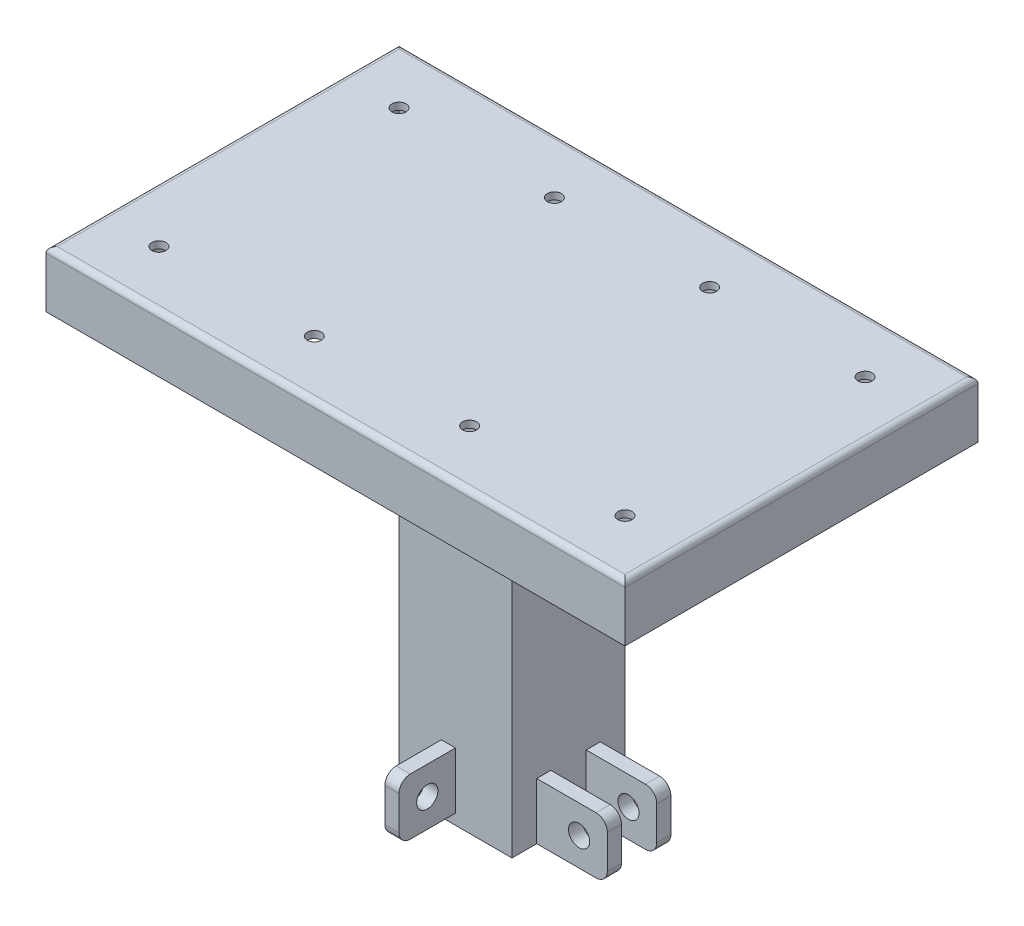
SolidWorks part; units mm, degrees
material "Alloy Steel"
ref_plane "Front Plane" through (0, 0, 0) normal (0, 0, 1) x (1, 0, 0)
ref_plane "Top Plane" through (0, 0, 0) normal (0, 1, 0) x (1, 0, 0)
ref_plane "Right Plane" through (0, 0, 0) normal (1, 0, 0) x (0, 0, -1)
other "Configuration Table"
sketch "Sketch1" plane through (0, 0, 0) normal (0, 1, 0) x (1, 0, 0)
  line L1 (-130.175, 79.375) -> (130.175, 79.375)
  line L2 (-130.175, 79.375) -> (-130.175, -79.375)
  line L3 (-130.175, -79.375) -> (130.175, -79.375)
  line L4 (130.175, 79.375) -> (130.175, -79.375)
  line L5 (-130.175, 79.375) -> (130.175, -79.375) construction
  line L6 (-130.175, -79.375) -> (130.175, 79.375) construction
  point P0 (0, 0)
  dimension "D1" = 260.35
  dimension "D2" = 158.75
extrude "Boss-Extrude1" add sketch "Sketch1" along normal blind 25.4
shell "Shell1" thickness 3.175 removed face at (0, 0, 0)
sketch "Sketch2" plane through (0, 22.225, 0) normal (0, -1, 0) x (1, 0, 0)
  line L1 (-25.4, 25.4) -> (25.4, 25.4)
  line L2 (-25.4, 25.4) -> (-25.4, -25.4)
  line L3 (-25.4, -25.4) -> (25.4, -25.4)
  line L4 (25.4, 25.4) -> (25.4, -25.4)
  line L5 (-25.4, 25.4) -> (25.4, -25.4) construction
  line L6 (-25.4, -25.4) -> (25.4, 25.4) construction
  point P0 (0, 0)
  dimension "D1" = 50.8
extrude "Boss-Extrude2" add sketch "Sketch2" along normal blind 184.15
shell "Shell2" thickness 3.175 removed face at (0, -161.925, 0)
sketch "Sketch4" plane through (0, 0, 0) normal (0, 0, 1) x (1, 0, 0)
  line L0 (25.4, -9.525) -> (63.5, 22.225)
  line L1 (25.4, -161.925) -> (25.4, 22.225) construction
  line L2 (123.0141, 22.225) -> (63.5, 22.225)
  line L4 (-130.175, 25.4) -> (130.175, 25.4) construction
  line L5 (25.4, -59.1201) -> (123.0141, 22.225)
  line L8 (63.5, 22.225) -> (25.4, 22.225) construction
  line L9 (-12.7, -90.8701) -> (168.7341, 60.325) construction
  line L10 (168.7341, 60.325) -> (-12.7, 60.325) construction
  line L11 (-12.7, 60.325) -> (-12.7, -90.8701) construction
  line L12 (25.4, -9.525) -> (25.4, -59.1201)
  line L14 (25.4, 22.225) -> (25.4, -9.525) construction
  dimension "D3" = 3.175
  dimension "D4" = 38.1
extrude "Boss-Extrude3" add sketch "Sketch4" along normal mid plane 6.35
mirror "Mirror1" about plane through (0, 0, 0) normal (1, 0, 0) of "Boss-Extrude3"
fillet "Fillet1" radius 2.54 4 edges at (-130.175, 25.4, 0) (0, 25.4, -79.375) (130.175, 25.4, 0) (0, 25.4, 79.375)
ref_plane "Plane1" through (0, 0, 14.2875) normal (0, 0, 1) x (1, 0, 0)
sketch "Sketch6" plane through (0, 0, 14.2875) normal (0, 0, 1) x (1, 0, 0)
  line L0 (25.4, -161.925) -> (57.15, -161.925)
  line L1 (57.15, -161.925) -> (57.15, -136.525)
  line L2 (57.15, -136.525) -> (25.4, -136.525)
  line L3 (25.4, -161.925) -> (25.4, 22.225) construction
  line L4 (25.4, -136.525) -> (25.4, -161.925)
  circle A0 centre (44.45, -149.225) radius 4.7625
  dimension "D3" = 9.525
  dimension "D1" = 31.75
  dimension "D2" = 25.4
  dimension "D4" = 12.7
  dimension "D5" = 12.7
extrude "Boss-Extrude4" add sketch "Sketch6" against normal blind 6.35
mirror "Mirror2" about plane through (0, 0, 0) normal (0, 0, 1) of "Boss-Extrude4"
fillet "Fillet2" radius 5.08 4 edges at (57.15, -161.925, -11.1125) (57.15, -136.525, -11.1125) (57.15, -161.925, 11.1125) (57.15, -136.525, 11.1125)
ref_plane "Plane2" through (0, 0, 0) normal (1, 0, 0) x (0, 0, -1)
sketch "Sketch7" plane through (0, 0, 0) normal (1, 0, 0) x (0, 0, -1)
  line L0 (-25.4, -157.1625) -> (-50.8, -157.1625)
  line L1 (-25.4, -161.925) -> (-25.4, 22.225) construction
  line L2 (-50.8, -157.1625) -> (-50.8, -131.7625)
  line L3 (-50.8, -131.7625) -> (-25.4, -131.7625)
  line L4 (-25.4, -131.7625) -> (-25.4, -157.1625)
  line L5 (-14.2875, -161.925) -> (-25.4, -161.925) construction
  circle A0 centre (-38.1, -144.4625) radius 4.7625
  dimension "D3" = 9.525
  dimension "D1" = 25.4
  dimension "D2" = 4.7625
  dimension "D4" = 12.7
  dimension "D5" = 12.7
extrude "Boss-Extrude5" add sketch "Sketch7" against normal blind 6.35
fillet "Fillet3" radius 5.08 2 edges at (-3.175, -157.1625, 50.8) (-3.175, -131.7625, 50.8)
mirror "Mirror3" about plane through (0, 0, 0) normal (0, 0, 1) of "Fillet3", "Boss-Extrude5"
hole_wizard "1/4 (0.25) Diameter Hole1" positions "Sketch8" profile "Sketch9" hole size "1/4" standard "ANSI Inch" end condition through all
sketch "Sketch8" plane through (0, 25.4, 0) normal (0, 1, 0) x (1, 0, 0)
  line L0 (-130.175, -79.375) -> (-130.175, 79.375) construction
  line L1 (-130.175, 79.375) -> (130.175, 79.375) construction
  line L2 (130.175, 79.375) -> (130.175, -79.375) construction
  point P0 (-104.775, 53.975)
  point P2 (-34.925, 53.975)
  point P4 (34.925, 53.975)
  point P6 (104.775, 53.975)
  dimension "D1" = 25.4
  dimension "D2" = 25.4
  dimension "D3" = 25.4
  dimension "D4" = 69.85
  dimension "D5" = 69.85
sketch "Sketch9" plane through (-104.775, 25.4, -53.975) normal (1, 0, 0) x (0, 0, 1)
  line L0 (0, 0) -> (0, 187.325)
  line L1 (0, 187.325) -> (3.175, 187.325)
  line L2 (3.175, 187.325) -> (3.175, 0)
  line L5 (3.175, 0) -> (0, 0)
  line L11 (0, -6.35) -> (0, 107.95) construction
  dimension "Thru Hole Dia." = 6.35
  dimension "Thru Hole Depth" = 187.325
mirror "Mirror4" about plane through (0, 0, 0) normal (0, 0, 1) of "1/4 (0.25) Diameter Hole1"
